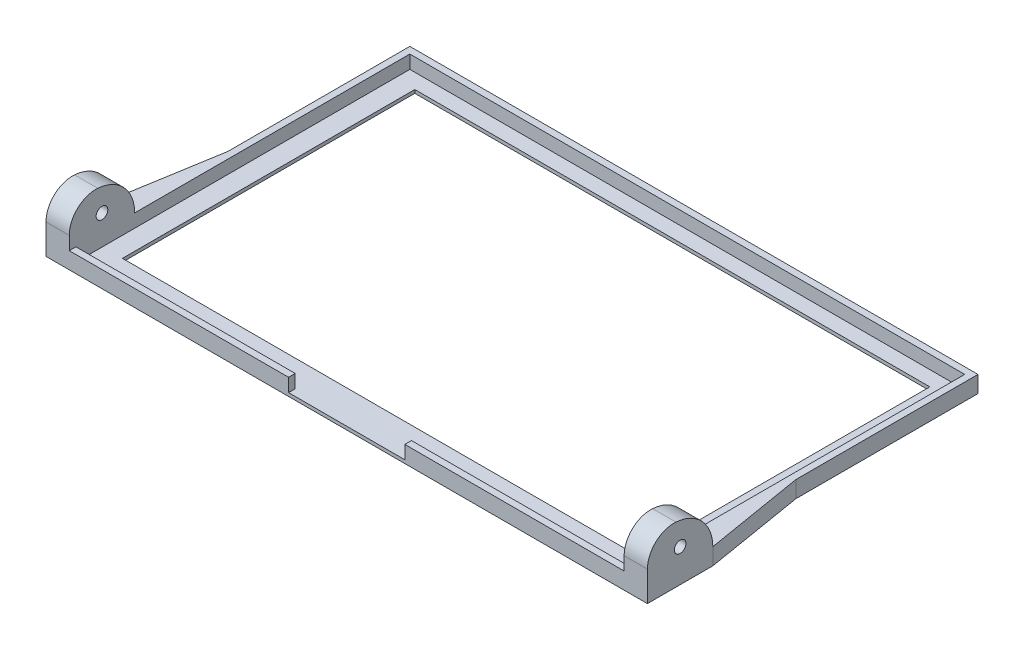
SolidWorks part; units mm, degrees
ref_plane "Front Plane" through (0, 0, 0) normal (0, 0, 1) x (1, 0, 0)
ref_plane "Top Plane" through (0, 0, 0) normal (0, 1, 0) x (1, 0, 0)
ref_plane "Right Plane" through (0, 0, 0) normal (1, 0, 0) x (0, 0, -1)
sketch "Sketch1" plane through (0, 0, 0) normal (0, 1, 0) x (1, 0, 0)
  line L0 (-85.5, 50.5) -> (85.5, 50.5)
  line L1 (-77.5, -44) -> (77.5, -44)
  line L2 (-77.5, -44) -> (-77.5, 44)
  line L3 (-77.5, 44) -> (77.5, 44)
  line L4 (77.5, -44) -> (77.5, 44)
  line L5 (-77.5, -44) -> (77.5, 44) construction
  line L6 (-77.5, 44) -> (77.5, -44) construction
  line L7 (85.5, 50.5) -> (85.5, -54)
  line L8 (85.5, -54) -> (-85.5, -54)
  line L9 (-85.5, -54) -> (-85.5, 50.5)
  point P0 (0, 0)
  point P9 (0, 0)
  point P11 (0, 0)
  point P12 (0, 0)
  point P13 (-83.6873, 49.4191)
  dimension "D1" = 155
  dimension "D2" = 88
  dimension "D3" = 8
  dimension "D4" = 8
  dimension "D5" = 6.5
  dimension "D6" = 10
extrude "Boss-Extrude1" add sketch "Sketch1" along normal blind 1
sketch "Sketch2" plane through (0, 1, 0) normal (0, 1, 0) x (1, 0, 0)
  line L0 (-83.5, 48.5) -> (-83.5, -52)
  line L1 (-83.5, -52) -> (83.5, -52)
  line L2 (83.5, -52) -> (83.5, 48.5)
  line L3 (83.5, 48.5) -> (-83.5, 48.5)
  line L4 (-85.5, 50.5) -> (-85.5, -54)
  line L5 (-85.5, -54) -> (85.5, -54)
  line L6 (85.5, -54) -> (85.5, 50.5)
  line L7 (85.5, 50.5) -> (-85.5, 50.5)
  line L8 (-85.5, 50.5) -> (-85.5, -54)
  line L9 (-85.5, -54) -> (85.5, -54)
  line L10 (85.5, -54) -> (85.5, 50.5)
  line L11 (85.5, 50.5) -> (-85.5, 50.5)
  dimension "D1" = 0
  dimension "D2" = 2
extrude "Boss-Extrude2" add sketch "Sketch2" along normal blind 4
sketch "Sketch3" plane through (0, 1, 0) normal (0, 1, 0) x (1, 0, 0)
  line L0 (0, 0) -> (0, -52) construction
  line L1 (-83.5, -52) -> (83.5, -52) construction
  line L3 (-17.5, -56.3497) -> (17.5, -56.3497)
  line L4 (-17.5, -56.3497) -> (-17.5, -47.6503)
  line L5 (-17.5, -47.6503) -> (17.5, -47.6503)
  line L6 (17.5, -56.3497) -> (17.5, -47.6503)
  line L7 (-17.5, -56.3497) -> (17.5, -47.6503) construction
  line L8 (-17.5, -47.6503) -> (17.5, -56.3497) construction
  dimension "D1" = 35
extrude "Cut-Extrude1" cut sketch "Sketch3" along normal blind 14
sketch "Sketch4" plane through (0, 1, 0) normal (0, 1, 0) x (1, 0, 0)
  line L0 (-83.5, 48.5) -> (-83.5, -52) construction
  line L1 (-83.5, -34.3044) -> (-90.5, -34.3044)
  line L2 (-83.5, -34.3044) -> (-83.5, -54)
  line L3 (-83.5, -54) -> (-90.5, -54)
  line L4 (-90.5, -34.3044) -> (-90.5, -54)
  line L5 (-85.5, -54) -> (-17.5, -54) construction
  line L6 (0, 0) -> (0, -54) construction
  line L7 (17.5, -54) -> (-17.5, -54) construction
  line L8 (83.5, -54) -> (90.5, -54)
  line L9 (90.5, -34.3044) -> (90.5, -54)
  line L10 (83.5, -34.3044) -> (90.5, -34.3044)
  line L11 (83.5, -34.3044) -> (83.5, -54)
  dimension "D1" = 7
extrude "Boss-Extrude3" add sketch "Sketch4" along normal blind 16 and the other way blind 1
fillet "Fillet1" radius 12 2 edges at (87, 17, 34.3044) (-87, 17, 34.3044)
chamfer "Chamfer1" distance 5 distance2 30 2 edges at (85.5, 2.5, 34.3044) (-85.5, 2.5, 34.3044) first distance on face at (88, 2.5, 34.3044) first distance on face at (-88, 2.5, 34.3044)
fillet "Fillet2" radius 8 2 edges at (87, 17, 54) (-87, 17, 54)
sketch "Sketch5" plane through (-90.5, 0, 0) normal (-1, 0, 0) x (0, 0, 1)
  line L0 (44.1522, 0) -> (44.1522, 9.8927) construction
  line L1 (34.3044, 0) -> (54, 0) construction
  circle A0 centre (44.1522, 9.8927) radius 1.75
extrude "Cut-Extrude2" cut sketch "Sketch5" against normal blind 216
